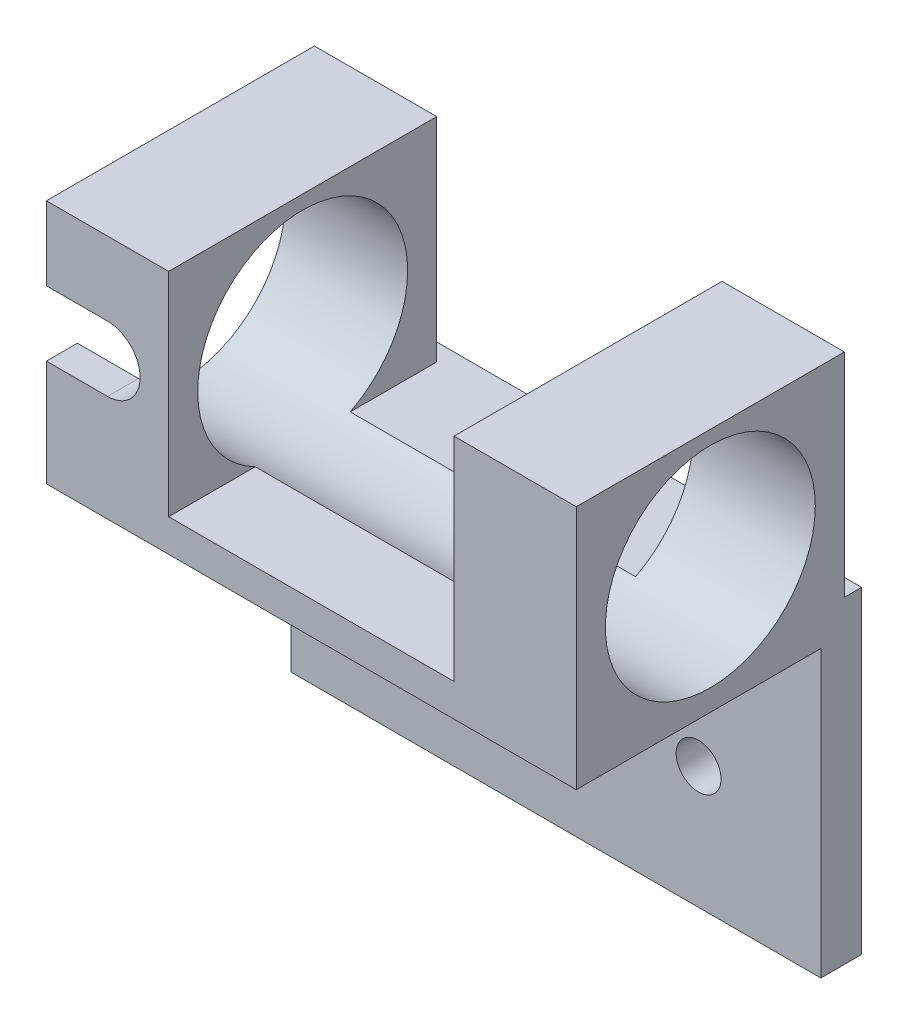
SolidWorks part; units mm, degrees
ref_plane "Alzado" through (0, 0, 0) normal (0, 0, 1) x (1, 0, 0)
ref_plane "Planta" through (0, 0, 0) normal (0, 1, 0) x (1, 0, 0)
ref_plane "Vista lateral" through (0, 0, 0) normal (1, 0, 0) x (0, 0, -1)
sketch "Croquis2" plane through (0, 0, 0) normal (0, 0, 1) x (1, 0, 0)
  line L1 (32.5, -23) -> (-32.5, -23)
  line L2 (32.5, -23) -> (32.5, 12)
  line L3 (32.5, 12) -> (-32.5, 12)
  line L4 (-32.5, -23) -> (-32.5, 12)
  circle A0 centre (-17.5, -8) radius 2.75
  circle A1 centre (17.5, -8) radius 2.75
  point P0 (0, 0)
  dimension "D3" = 5.5
  dimension "D4" = 5.5
  dimension "D1" = 35
  dimension "D2" = 65
  dimension "D5" = 15
  dimension "D6" = 15
  dimension "D7" = 15
  dimension "D8" = 15
extrude "Saliente-Extruir1" add sketch "Croquis2" along normal blind 5 contours L4 L1 L2 L3 A1 A0 region at (0, -5.4467, 0)
sketch "Croquis3" plane through (0, 12, 0) normal (0, 1, 0) x (1, 0, 0)
  line L1 (-32.5, 0) -> (32.5, 0)
  line L2 (-32.5, 0) -> (-32.5, -35)
  line L3 (-32.5, -35) -> (32.5, -35)
  line L4 (32.5, 0) -> (32.5, -35)
  dimension "D1" = 35
  dimension "D2" = 65
extrude "Saliente-Extruir2" add sketch "Croquis3" along normal blind 4
sketch "Croquis4" plane through (32.5, 0, 0) normal (1, 0, 0) x (0, 0, -1)
  line L0 (-35, 16) -> (-2.1175, 16) construction
  line L1 (-35, 16) -> (0, 16) construction
  line L2 (-35, 16) -> (-35, 42.0613)
  line L3 (-35, 42.0613) -> (-2.1175, 42.0613)
  line L4 (-2.1175, 42.0613) -> (-2.1175, 16)
  circle A0 centre (-18.5588, 27.4824) radius 12.875
  point P9 (-18.5588, 16)
  line M2 (0, 16) -> (-35, 16)
  dimension "D1" = 25.75
extrude "Saliente-Extruir3" add sketch "Croquis4" against normal blind 15 contours A0 L4 L3 L2 M2 | A0 M2 region at (32.5, 29.0307, 34.5804) region at (32.5, 27.7407, 18.5588)
extrude "Saliente-Extruir4" add sketch "Croquis4<6>" along normal blind 15 from surface contours A0 L4 L3 L2 M2 | A0 M2 region at (32.5, 29.0307, 34.5804) region at (32.5, 27.7407, 18.5588) starting at face at (-32.5, 1.6667, 13.3333)
sketch "Croquis4<6>" plane through (32.5, 0, 0) normal (1, 0, 0) x (0, 0, -1) same geometry as "Croquis4"
extrude "Cortar-Extruir1" cut sketch "Croquis4<4>" against normal through all contours A0 M2 | A0 M2 region at (32.5, 15.4403, 18.5588) region at (32.5, 27.7407, 18.5588)
sketch "Croquis4<4>" plane through (32.5, 0, 0) normal (1, 0, 0) x (0, 0, -1) same geometry as "Croquis4"
sketch "Croquis5" plane through (0, 0, 2.1175) normal (0, 0, -1) x (-1, 0, 0)
  line L0 (17.5, 16) -> (32.5, 16) construction
  line L5 (32.5, 33.0307) -> (25, 33.0307)
  line L6 (25, 25.0307) -> (32.5, 25.0307)
  line L7 (32.5, 16) -> (32.5, 42.0613) construction
  line L8 (17.5, 16) -> (32.5, 16)
  line L9 (32.5, 16) -> (32.5, 42.0613)
  line L10 (32.5, 25.0307) -> (32.5, 33.0307)
  arc A0 (25, 33.0307) -> (25, 25.0307) centre (25, 29.0307) ccw
  point P8 (32.5, 29.0307)
  dimension "D1" = 8
  dimension "D2" = 7.5
extrude "Cortar-Extruir2" cut sketch "Croquis5" along normal blind 9 from surface contours A0 region at (-27.1418, 29.0307, 2.1175) starting at face at (0, 28.0307, 35)
sketch "Croquis6" plane through (-32.5, 0, 0) normal (-1, 0, 0) x (0, 0, 1)
  line L8 (0, 16) -> (0, -23)
  line L9 (0, -23) -> (5, -23)
  line L10 (5, -23) -> (5, 12)
  line L11 (5, 12) -> (35, 12)
  line L12 (35, 12) -> (35, 25.0307)
  line L13 (35, 42.0613) -> (2.1175, 42.0613)
  line L14 (2.1175, 42.0613) -> (2.1175, 16)
  line L15 (2.1175, 16) -> (0, 16)
  line L16 (0, 16) -> (0, -23)
  line L17 (0, -23) -> (5, -23)
  line L18 (5, -23) -> (5, 12)
  line L19 (5, 12) -> (35, 12)
  line L20 (35, 12) -> (35, 25.0307)
  line L21 (35, 42.0613) -> (2.1175, 42.0613)
  line L22 (2.1175, 42.0613) -> (2.1175, 16)
  line L23 (2.1175, 16) -> (0, 16)
  line L27 (30.177, 33.0307) -> (35, 33.0307)
  line L28 (30.177, 33.0307) -> (35, 33.0307)
  line L29 (35, 33.0307) -> (35, 42.0613)
  line L30 (35, 33.0307) -> (35, 42.0613)
  line L31 (35, 25.0307) -> (31.1982, 25.0307)
  line L32 (35, 25.0307) -> (31.1982, 25.0307)
  arc A1 (30.177, 33.0307) -> (31.1982, 25.0307) centre (18.5588, 27.4824) ccw
  arc A2 (31.5305, 33.6771) -> (32.6707, 24.745) centre (18.5588, 27.4824) ccw
  circle A3 centre (18.5588, 27.4824) radius 14.375
  arc A4 (30.177, 33.0307) -> (31.1982, 25.0307) centre (18.5588, 27.4824) ccw
  dimension "D1" = 0
  dimension "D2" = 1.5
